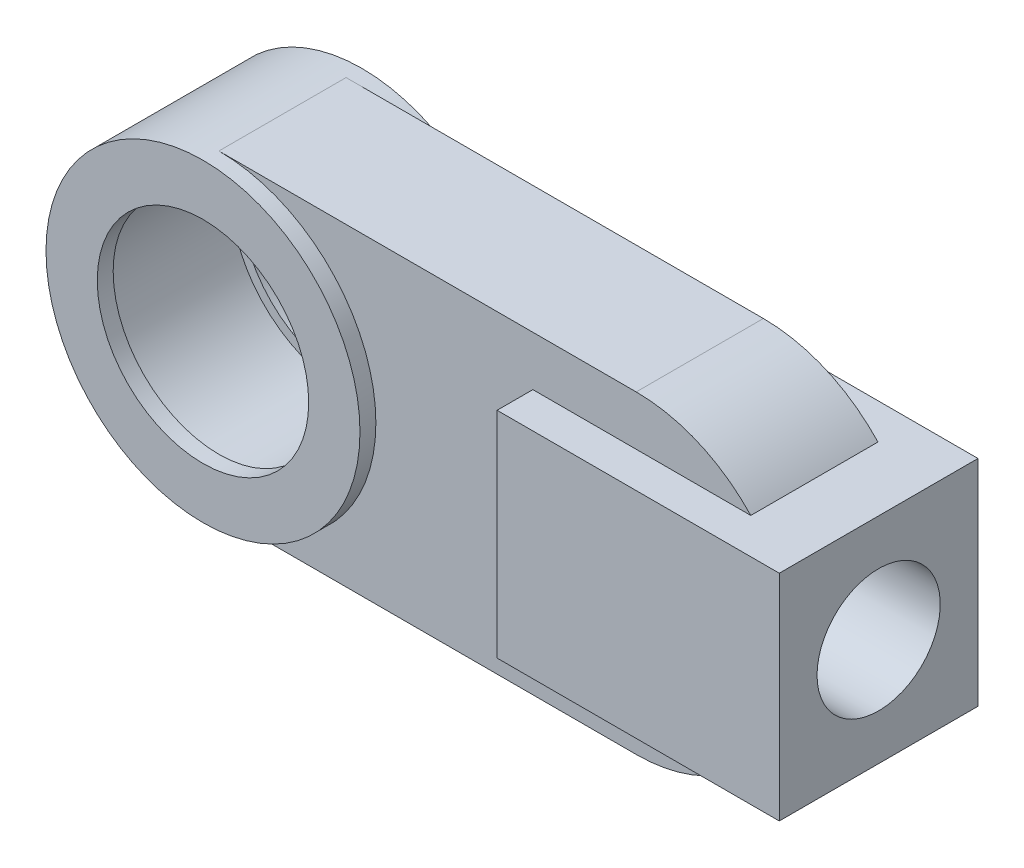
SolidWorks part; units mm, degrees
ref_plane "Front Plane" through (0, 0, 0) normal (0, 0, 1) x (1, 0, 0)
ref_plane "Top Plane" through (0, 0, 0) normal (0, 1, 0) x (1, 0, 0)
ref_plane "Right Plane" through (0, 0, 0) normal (1, 0, 0) x (0, 0, -1)
sketch "S01 - Socket head and shank" plane through (0, 0, 0) normal (0, 0, 1) x (1, 0, 0)
  line L0 (0, 3.95) -> (10.5, 3.95)
  line L1 (10.5, -3.95) -> (0, -3.95)
  arc A0 (10.5, 3.95) -> (10.5, -3.95) centre (10.5, 0) cw
  arc A1 (0, -3.95) -> (0, 3.95) centre (0, 0) cw
  dimension "D1" = 3.95
  dimension "D2" = 10.5
extrude "01 - Socket head and shank" add sketch "S01 - Socket head and shank" along normal blind 3.2 from offset 1.6 offset against normal yes
sketch "S02 - Articulation opening" plane through (0, 0, 0) normal (0, 0, 1) x (1, 0, 0)
  circle A0 centre (0, 0) radius 2.9
  dimension "D1" = 5.8
extrude "02 - Articulation opening" cut sketch "S02 - Articulation opening" along normal blind 4 from offset 2 offset against normal yes
sketch "S03 - Captive spherical seat lip 1" plane through (0, 0, 0) normal (0, 0, 1) x (1, 0, 0)
  circle A0 centre (0, 0) radius 3.95
  circle A1 centre (0, 0) radius 2.66
  dimension "D1" = 5.32
  dimension "D2" = 7.9
extrude "03 - Captive spherical seat lip 1" add sketch "S03 - Captive spherical seat lip 1" along normal blind 0.4 from offset 2 offset against normal yes
sketch "S04 - Captive spherical seat lip 2" plane through (0, 0, 0) normal (0, 0, 1) x (1, 0, 0)
  circle A0 centre (0, 0) radius 3.95
  circle A1 centre (0, 0) radius 2.66
  dimension "D1" = 5.32
  dimension "D2" = 7.9
extrude "04 - Captive spherical seat lip 2" add sketch "S04 - Captive spherical seat lip 2" along normal blind 0.4 from offset 1.6
sketch "S05 - Rod thread boss" plane through (0, 0, 0) normal (0, 0, 1) x (1, 0, 0)
  line L0 (7.9, -2.7) -> (15, -2.7)
  line L1 (15, -2.7) -> (15, 2.7)
  line L2 (15, 2.7) -> (7.9, 2.7)
  line L3 (7.9, 2.7) -> (7.9, -2.7)
  dimension "D1" = 7.9
  dimension "D2" = 15
  dimension "D3" = 2.7
  dimension "D4" = 2.7
extrude "05 - Rod thread boss" add sketch "S05 - Rod thread boss" along normal blind 5 from offset 2.5 offset against normal yes
sketch3d "Plane points - M3 internal thread envelope"
  point P0 (0, 0, 0)
  point P1 (0, 18, 0)
  point P2 (0, 0, 18)
ref_plane "Drilling plane - M3 internal thread envelope" through (0, 0, 0) normal (1, 0, 0) x (0, 0, -1)
sketch "S06 - M3 internal thread envelope" plane through (0, 0, 0) normal (1, 0, 0) x (0, 0, -1)
  circle A0 centre (0, 0) radius 1.55
  dimension "D1" = 3.1
extrude "06 - M3 internal thread envelope" cut sketch "S06 - M3 internal thread envelope" along normal blind 9 from offset 7
